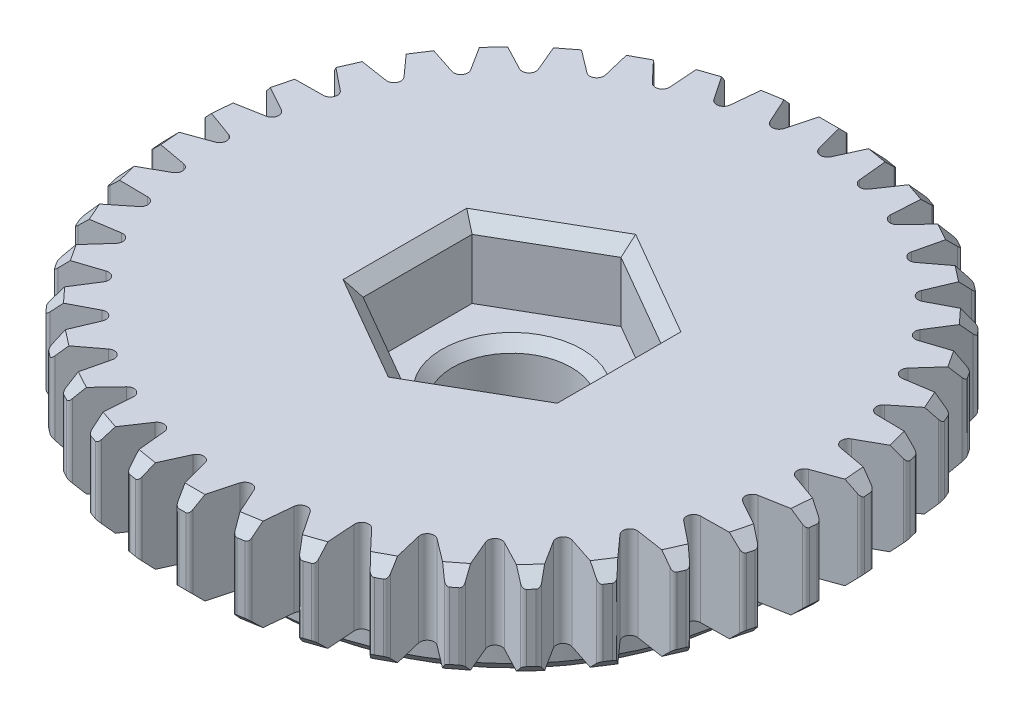
SolidWorks part; units mm, degrees
material "PET"
ref_plane "Front" through (0, 0, 0) normal (0, 0, 1) x (1, 0, 0)
ref_plane "Top" through (0, 0, 0) normal (0, 1, 0) x (1, 0, 0)
ref_plane "Right" through (0, 0, 0) normal (1, 0, 0) x (0, 0, -1)
sketch "Sketch1" plane through (0, 0, 0) normal (0, 1, 0) x (1, 0, 0)
  line L1 (-5.6833, 3.2812) -> (-5.6832, -3.2812)
  line L2 (-5.6832, -3.2812) -> (0, -6.5625)
  line L3 (0, -6.5625) -> (5.6833, -3.2812)
  line L4 (5.6833, -3.2812) -> (5.6832, 3.2812)
  line L5 (5.6832, 3.2812) -> (0, 6.5625)
  line L6 (0, 6.5625) -> (-5.6833, 3.2812)
  circle A0 centre (0, 0) radius 5.6833 construction
  circle A1 centre (0, 0) radius 17.4625
  dimension "D1" = 11.3665
  dimension "D2" = 34.925
extrude "Boss-Extrude1" add sketch "Sketch1" along normal blind 5.5562
ref_axis "Axis1" through (0, 50, 0) along (0, -1, 0)
sketch "Sketch2" plane through (0, 5.5562, 0) normal (0, 1, 0) x (1, 0, 0)
  line L0 (0, 0) -> (0, 17.4625) construction
  line L1 (0, 17.4625) -> (0, 19.8438) construction
  line L5 (-0.3969, 19.8438) -> (0.3969, 19.8438)
  line L6 (0.3969, 19.8438) -> (1.0433, 17.4313)
  line L7 (0, 17.4625) -> (1.0433, 17.4313)
  line L8 (0, 17.4625) -> (-1.0433, 17.4313)
  line L9 (-0.3969, 19.8438) -> (-1.0433, 17.4313)
  circle A0 centre (0, 0) radius 17.4625 construction
  dimension "D1" = 0.3969
  dimension "D2" = 2.3812
  dimension "D3" = 15
extrude "Boss-Extrude3" add sketch "Sketch2" against normal through all
chamfer "Chamfer3" distance 0.762 angle 45 2 edges at (0, 0, -19.8438) (0, 5.5562, -19.8438)
fillet "Fillet2" [suppressed] radius 0.762
fillet "Fillet3" radius 0.25 2 edges at (0.3969, 2.7781, -19.8438) (-0.3969, 2.7781, -19.8438)
pattern_circular "CirPattern2" count 38 over 360 about axis through (0, 5.5562, 0) along (0, 1, 0) of "Boss-Extrude3", "Fillet2", "Chamfer3", "Fillet3"
sketch "Sketch4" plane through (0, 5.5562, 0) normal (0, 1, 0) x (1, 0, 0)
  line L0 (1.0433, 17.4313) -> (0.6011, 19.0818) construction
  line L1 (2.5479, 18.9204) -> (1.84, 17.3653) construction
  circle A0 centre (1.4535, 17.5412) radius 0.4247
extrude "Cut-Extrude1" cut sketch "Sketch4" against normal through all
pattern_circular "CirPattern6" count 38 over 360 about axis through (0, 50, 0) along (0, -1, 0) of "Cut-Extrude1"
sketch "Sketch3" plane through (0, 0, 0) normal (0, -1, 0) x (1, 0, 0)
  line L6 (-5.6833, -3.2812) -> (0, -6.5625)
  line L7 (-5.6832, 3.2812) -> (-5.6833, -3.2812)
  line L8 (0, 6.5625) -> (-5.6832, 3.2812)
  line L9 (5.6833, 3.2812) -> (0, 6.5625)
  line L10 (5.6832, -3.2812) -> (5.6833, 3.2812)
  line L11 (0, -6.5625) -> (5.6832, -3.2812)
  line L12 (-5.6833, -3.2812) -> (0, -6.5625)
  line L13 (-5.6832, 3.2812) -> (-5.6833, -3.2812)
  line L14 (0, 6.5625) -> (-5.6832, 3.2812)
  line L15 (5.6833, 3.2812) -> (0, 6.5625)
  line L16 (5.6832, -3.2812) -> (5.6833, 3.2812)
  line L17 (0, -6.5625) -> (5.6832, -3.2812)
  circle A0 centre (0, 0) radius 15.113
  dimension "D1" = 30.226
  dimension "D2" = 0
extrude "Boss-Extrude4" add sketch "Sketch3" along normal blind 3.175
chamfer "Chamfer1" distance 0.762 angle 45 7 edges at (-5.6832, 5.5562, 0) (-2.8416, 5.5562, 4.9218) (2.8416, 5.5562, 4.9218) (5.6832, 5.5562, 0) (2.8416, 5.5562, -4.9218) (-2.8416, 5.5562, -4.9218) (0, -3.175, -15.113)
sketch "Sketch5" plane through (0, -3.175, 0) normal (0, -1, 0) x (1, 0, 0)
  line L7 (5.6832, -3.2812) -> (5.6833, 3.2812)
  line L8 (0, -6.5625) -> (5.6832, -3.2812)
  line L9 (-5.6832, -3.2812) -> (0, -6.5625)
  line L10 (-5.6832, 3.2812) -> (-5.6832, -3.2812)
  line L11 (0, 6.5625) -> (-5.6832, 3.2812)
  line L12 (5.6833, 3.2812) -> (0, 6.5625)
  line L13 (5.6832, -3.2812) -> (5.6833, 3.2812)
  line L14 (0, -6.5625) -> (5.6832, -3.2812)
  line L15 (-5.6832, -3.2812) -> (0, -6.5625)
  line L16 (-5.6832, 3.2812) -> (-5.6832, -3.2812)
  line L17 (0, 6.5625) -> (-5.6832, 3.2812)
  line L18 (5.6833, 3.2812) -> (0, 6.5625)
  dimension "D1" = 0
extrude "Boss-Extrude5" add sketch "Sketch5" against normal blind 4.3656
hole_wizard "1/4 Clearance Hole1" positions "Sketch6" profile "Sketch8" hole size "1/4" standard "ANSI Inch" end condition through all
sketch "Sketch6" plane through (0, -3.175, 0) normal (0, -1, 0) x (-1, 0, 0)
  point P0 (0, 0)
sketch "Sketch8" plane through (0, -3.175, 0) normal (1, 0, 0) x (0, 0, -1)
  line L0 (0, 0) -> (0, 4.3656)
  line L1 (0, 4.3656) -> (4.2062, 4.3656)
  line L2 (3.5712, 3.7306) -> (3.5712, 0.635)
  line L3 (3.5712, 0.635) -> (4.2062, 0)
  line L5 (4.2062, 0) -> (0, 0)
  line L6 (-3.5712, 0.635) -> (-4.2062, 0) construction
  line L7 (4.2062, 4.3656) -> (3.5712, 3.7306)
  line L8 (-4.2062, 4.3656) -> (-3.5712, 3.7306) construction
  line L11 (0, -6.35) -> (0, 107.95) construction
  dimension "Thru Hole Dia." = 7.1425
  dimension "Thru Hole Depth" = 4.3656
  dimension "Near C'Sink Dia." = 8.4125
  dimension "Near C'Sink Angle" = 90
  dimension "Far C'Sink Dia." = 8.4125
  dimension "Far C'Sink Angle" = 90
